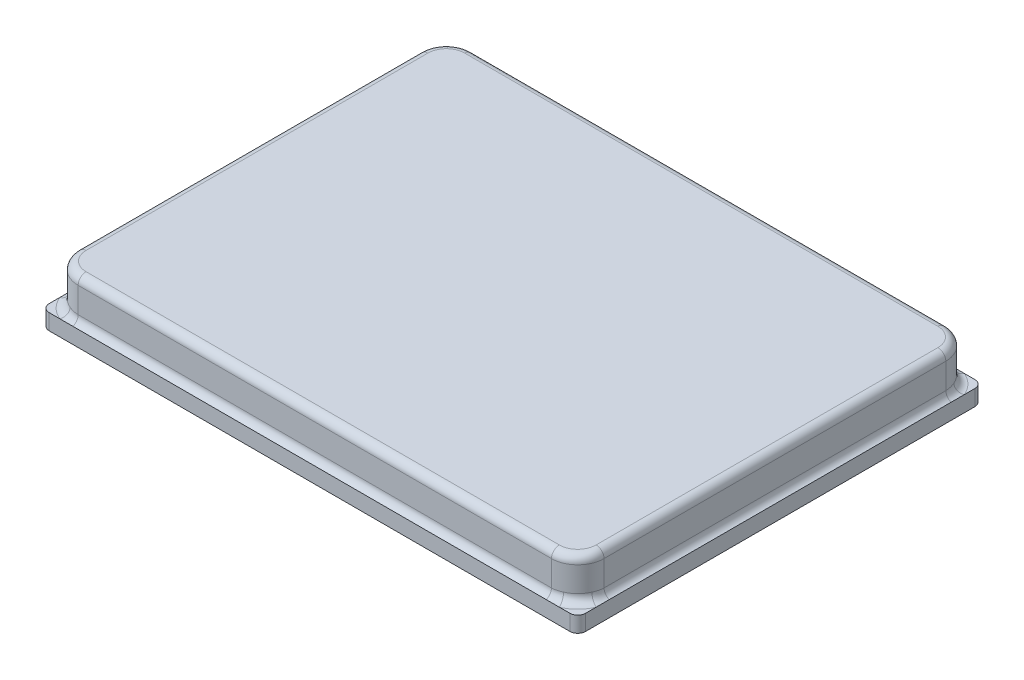
SolidWorks part; units mm, degrees
ref_plane "Front Plane" through (0, 0, 0) normal (0, 0, 1) x (1, 0, 0)
ref_plane "Top Plane" through (0, 0, 0) normal (0, 1, 0) x (1, 0, 0)
ref_plane "Right Plane" through (0, 0, 0) normal (1, 0, 0) x (0, 0, -1)
sketch "Sketch1" plane through (0, 0, 0) normal (0, 1, 0) x (1, 0, 0)
  line L0 (5.25, 5.25) -> (5.25, 144.75)
  line L1 (0, 0) -> (200, 0)
  line L2 (0, 0) -> (0, 150)
  line L3 (0, 150) -> (200, 150)
  line L4 (200, 0) -> (200, 150)
  line L5 (5.25, 144.75) -> (194.75, 144.75)
  line L6 (194.75, 5.25) -> (194.75, 144.75)
  line L7 (5.25, 5.25) -> (194.75, 5.25)
  line L8 (0, 150) -> (18.9, 131.1) construction
  line L9 (5.25, 144.75) -> (18.9, 144.75) construction
  line L10 (5.25, 144.75) -> (5.25, 131.1) construction
  line L11 (5.25, 131.1) -> (18.9, 131.1) construction
  line L12 (18.9, 144.75) -> (18.9, 131.1) construction
  line L13 (194.75, 144.75) -> (181.1, 144.75) construction
  line L14 (194.75, 144.75) -> (194.75, 131.1) construction
  line L15 (194.75, 131.1) -> (181.1, 131.1) construction
  line L16 (181.1, 144.75) -> (181.1, 131.1) construction
  line L17 (5.25, 5.25) -> (18.9, 5.25) construction
  line L18 (5.25, 5.25) -> (5.25, 18.9) construction
  line L19 (5.25, 18.9) -> (18.9, 18.9) construction
  line L20 (18.9, 5.25) -> (18.9, 18.9) construction
  line L21 (18.9, 144.75) -> (18.9, 140.1538)
  line L22 (100, 150) -> (100, 0) construction
  line L23 (9.8462, 131.1) -> (5.25, 131.1)
  line L24 (190.1538, 131.1) -> (194.75, 131.1)
  line L25 (200, 75) -> (0, 75) construction
  line L26 (181.1, 144.75) -> (181.1, 140.1538)
  line L27 (0, 0) -> (18.9, 18.9) construction
  line L28 (5.25, 18.9) -> (9.8462, 18.9)
  line L29 (18.9, 9.8462) -> (18.9, 5.25)
  line L30 (181.1, 9.8462) -> (181.1, 5.25)
  line L31 (194.75, 18.9) -> (190.1538, 18.9)
  circle A0 centre (9.8462, 140.1538) radius 6.5 construction
  circle A1 centre (9.8462, 140.1538) radius 3
  arc A2 (9.8462, 131.1) -> (18.9, 140.1538) centre (9.8462, 140.1538) ccw
  circle A3 centre (190.1538, 140.1538) radius 3
  arc A4 (190.1538, 131.1) -> (181.1, 140.1538) centre (190.1538, 140.1538) cw
  circle A5 centre (9.8462, 9.8462) radius 6.5 construction
  circle A6 centre (9.8462, 9.8462) radius 3
  arc A7 (18.9, 9.8462) -> (9.8462, 18.9) centre (9.8462, 9.8462) ccw
  arc A8 (181.1, 9.8462) -> (190.1538, 18.9) centre (190.1538, 9.8462) cw
  circle A9 centre (190.1538, 140.1538) radius 3
  circle A10 centre (190.1538, 9.8462) radius 3
  dimension "D6" = 13
  dimension "D7" = 6
  dimension "D8" = 13
  dimension "D1" = 150
  dimension "D2" = 200
  dimension "D4" = 162.2
  dimension "D5" = 112.2
  dimension "D3" = 5.25
extrude "Boss-Extrude1" add sketch "Sketch1" along normal blind 15.5 contours L1 L4 L3 L2 L7 L0 L5 L6 | L29 A7 L28 L0 L7 A6 | L23 A2 L21 L5 L0 A1 | A4 L24 L6 L5 L26 A3 | A8 L30 L7 L6 L31 A10 region at (5.443, 0, -12.075) region at (5.443, 0, -137.925) region at (181.293, 0, -7.5481) region at (187.925, 0, -144.557) region at (2.5, 0, -75)
sketch "Sketch2" plane through (0, 15.5, 0) normal (0, 1, 0) x (1, 0, 0)
  line L1 (0, 150) -> (200, 150)
  line L2 (0, 150) -> (0, 0)
  line L3 (0, 0) -> (200, 0)
  line L4 (200, 150) -> (200, 0)
extrude "Boss-Extrude2" add sketch "Sketch2" along normal blind 5
sketch "Sketch3" plane through (0, 0, 0) normal (0, -1, 0) x (1, 0, 0)
  line L14 (18.9, -5.25) -> (181.1, -5.25) construction
  line L15 (5.25, -5.25) -> (194.75, -5.25)
  line L16 (5.25, -5.25) -> (5.25, -144.75)
  line L17 (5.25, -144.75) -> (194.75, -144.75)
  line L18 (202, -152) -> (202, 2)
  line L19 (-2, -152) -> (202, -152)
  line L20 (-2, 2) -> (-2, -152)
  line L21 (202, 2) -> (-2, 2)
  line L22 (202, -152) -> (202, 2)
  line L23 (-2, -152) -> (202, -152)
  line L24 (-2, 2) -> (-2, -152)
  line L25 (202, 2) -> (-2, 2)
  line L26 (194.75, -5.25) -> (194.75, -144.75)
  line L27 (5.25, -18.9) -> (5.25, -131.1) construction
  line L28 (18.9, -144.75) -> (181.1, -144.75) construction
  line L29 (194.75, -18.9) -> (194.75, -131.1) construction
  dimension "D1" = 2
extrude "Boss-Extrude3" add sketch "Sketch3" against normal blind 5
sketch "Sketch4" plane through (0, 0, 0) normal (0, -1, 0) x (1, 0, 0)
  line L0 (0, 0) -> (0, -150)
  line L1 (-2, 2) -> (202, 2)
  line L2 (-2, 2) -> (-2, -152)
  line L3 (-2, -152) -> (202, -152)
  line L4 (202, 2) -> (202, -152)
  line L5 (0, -150) -> (200, -150)
  line L6 (200, 0) -> (200, -150)
  line L7 (0, 0) -> (200, 0)
  dimension "D1" = 2
extrude "Boss-Extrude4" add sketch "Sketch4" along normal blind 1
fillet "Fillet1" radius 10 4 edges at (200, 12.75, -150) (200, 12.75, 0) (0, 12.75, -150) (0, 12.75, 0)
fillet "Fillet2" radius 3 15 edges at (197.0711, 5, -2.9289) (197.0711, 5, -147.0711) (2.9289, 5, -147.0711) (197.0711, 20.5, -2.9289) (100, 20.5, 0) (2.9289, 20.5, -2.9289) (0, 20.5, -75) (2.9289, 20.5, -147.0711) (100, 20.5, -150) (197.0711, 20.5, -147.0711) (200, 20.5, -75) (2.9289, 5, -2.9289) (-2, 2, 2) (202, 2, 2) (202, 2, -152)
